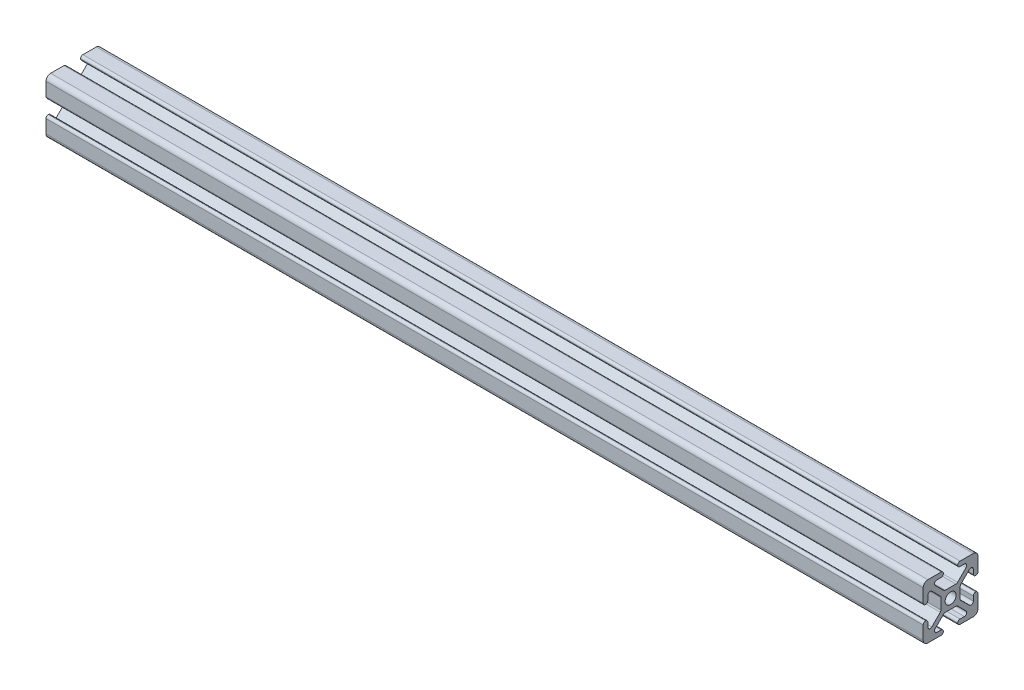
SolidWorks part; units mm, degrees
ref_plane "Front Plane" through (0, 0, 0) normal (1, 0, 0) x (0, 1, 0)
ref_plane "Top Plane" through (0, 0, 0) normal (0, 0, 1) x (0, 1, 0)
ref_plane "Right Plane" through (0, 0, 0) normal (0, 1, 0) x (-1, 0, 0)
sketch "Sketch1" plane through (0, 0, 0) normal (1, 0, 0) x (0, 1, 0)
  line L0 (0, 0) -> (0, 12.5) construction
  line L1 (-12.5, -12.5) -> (12.5, -12.5)
  line L2 (-12.5, -12.5) -> (-12.5, 12.5)
  line L3 (-12.5, 12.5) -> (12.5, 12.5)
  line L4 (12.5, -12.5) -> (12.5, 12.5)
  line L5 (-12.5, -12.5) -> (12.5, 12.5) construction
  line L6 (-12.5, 12.5) -> (12.5, -12.5) construction
  line L7 (-3.25, 12.5) -> (-3.25, 10.37)
  line L8 (-3.25, 10.37) -> (-8.8639, 10.37)
  line L9 (-8.8639, 10.37) -> (-2.8739, 4.38)
  line L10 (-2.8739, 4.38) -> (2.8739, 4.38)
  line L11 (8.8639, 10.37) -> (2.8739, 4.38)
  line L12 (3.25, 10.37) -> (8.8639, 10.37)
  line L13 (3.25, 12.5) -> (3.25, 10.37)
  line L14 (12.5, -3.25) -> (10.37, -3.25)
  line L15 (10.37, -3.25) -> (10.37, -8.8639)
  line L16 (10.37, -8.8639) -> (4.38, -2.8739)
  line L17 (4.38, 2.8739) -> (4.38, -2.8739)
  line L18 (10.37, 8.8639) -> (4.38, 2.8739)
  line L19 (10.37, 3.25) -> (10.37, 8.8639)
  line L20 (12.5, 3.25) -> (10.37, 3.25)
  line L21 (-3.25, -12.5) -> (-3.25, -10.37)
  line L22 (-3.25, -10.37) -> (-8.8639, -10.37)
  line L23 (-8.8639, -10.37) -> (-2.8739, -4.38)
  line L24 (2.8739, -4.38) -> (-2.8739, -4.38)
  line L25 (8.8639, -10.37) -> (2.8739, -4.38)
  line L26 (3.25, -10.37) -> (8.8639, -10.37)
  line L27 (3.25, -12.5) -> (3.25, -10.37)
  line L28 (-12.5, 3.25) -> (-10.37, 3.25)
  line L29 (-10.37, 3.25) -> (-10.37, 8.8639)
  line L30 (-10.37, 8.8639) -> (-4.38, 2.8739)
  line L31 (-4.38, -2.8739) -> (-4.38, 2.8739)
  line L32 (-10.37, -8.8639) -> (-4.38, -2.8739)
  line L33 (-10.37, -3.25) -> (-10.37, -8.8639)
  line L34 (-12.5, -3.25) -> (-10.37, -3.25)
  circle A0 centre (0, 0) radius 2.5
  point P0 (0, 0)
  point P15 (0, 4.38)
  dimension "D3" = 5
  dimension "D1" = 25
  dimension "D2" = 25
  dimension "D4" = 2.13
  dimension "D5" = 2.13
  dimension "D6" = 6.5
  dimension "D7" = 4.38
  dimension "D8" = 4
extrude "Boss-Extrude1" add sketch "Sketch1" along normal blind 400 contours L34 L2 L1 L21 L22 L23 L24 L25 L26 L27 L4 L14 L15 L16 L17 L18 L19 L20 L3 L13 L12 L11 L10 L9 L8 L7 L28 L29 L30 L31 L32 L33 A0 region at (0, -12.1464, -7.875)
fillet "Fillet1" radius 1.065 32 edges at (200, -10.37, -8.8639) (200, 2.8739, -4.38) (200, -2.8739, -4.38) (200, -4.38, 2.8739) (200, -4.38, -2.8739) (200, -2.8739, 4.38) (200, 2.8739, 4.38) (200, 4.38, 2.8739) (200, 4.38, -2.8739) (200, -8.8639, -10.37) (200, 8.8639, -10.37) (200, 10.37, -8.8639) (200, -10.37, 8.8639) (200, -8.8639, 10.37) (200, 10.37, 8.8639) (200, 8.8639, 10.37) (200, 12.5, 3.25) (200, -3.25, -12.5) (200, -10.37, 3.25) (200, 10.37, 3.25) (200, -10.37, -3.25) (200, -12.5, -3.25) (200, -12.5, 3.25) (200, 3.25, -10.37) (200, -3.25, -10.37) (200, 3.25, -12.5) (200, 10.37, -3.25) (200, 12.5, -3.25) (200, 3.25, 12.5) (200, 3.25, 10.37) (200, -3.25, 10.37) (200, -3.25, 12.5)
fillet "Fillet2" radius 2.13 4 edges at (200, 12.5, -12.5) (200, -12.5, -12.5) (200, 12.5, 12.5) (200, -12.5, 12.5)
sketch "Sketch2" plane through (400, 0, 0) normal (1, 0, 0) x (0, 1, 0)
  line L0 (10.37, -12.5) -> (4.315, -12.5)
  line L1 (10.37, -12.5) -> (4.315, -12.5)
  line L2 (4.315, -10.37) -> (6.2927, -10.37)
  line L3 (4.315, -10.37) -> (6.2927, -10.37)
  line L4 (7.0458, -8.5519) -> (3.1858, -4.6919)
  line L5 (7.0458, -8.5519) -> (3.1858, -4.6919)
  line L6 (2.4327, -4.38) -> (-2.4327, -4.38)
  line L7 (2.4327, -4.38) -> (-2.4327, -4.38)
  line L8 (-3.1858, -4.6919) -> (-7.0458, -8.5519)
  line L9 (-3.1858, -4.6919) -> (-7.0458, -8.5519)
  line L10 (-6.2927, -10.37) -> (-4.315, -10.37)
  line L11 (-6.2927, -10.37) -> (-4.315, -10.37)
  line L12 (-4.315, -12.5) -> (-10.37, -12.5)
  line L13 (-4.315, -12.5) -> (-10.37, -12.5)
  line L14 (-12.5, -10.37) -> (-12.5, -4.315)
  line L15 (-12.5, -10.37) -> (-12.5, -4.315)
  line L16 (-10.37, -4.315) -> (-10.37, -6.2927)
  line L17 (-10.37, -4.315) -> (-10.37, -6.2927)
  line L18 (-8.5519, -7.0458) -> (-4.6919, -3.1858)
  line L19 (-8.5519, -7.0458) -> (-4.6919, -3.1858)
  line L20 (-4.38, -2.4327) -> (-4.38, 2.4327)
  line L21 (-4.38, -2.4327) -> (-4.38, 2.4327)
  line L22 (-4.6919, 3.1858) -> (-8.5519, 7.0458)
  line L23 (-4.6919, 3.1858) -> (-8.5519, 7.0458)
  line L24 (-10.37, 6.2927) -> (-10.37, 4.315)
  line L25 (-10.37, 6.2927) -> (-10.37, 4.315)
  line L26 (-12.5, 4.315) -> (-12.5, 10.37)
  line L27 (-12.5, 4.315) -> (-12.5, 10.37)
  line L28 (-10.37, 12.5) -> (-4.315, 12.5)
  line L29 (-10.37, 12.5) -> (-4.315, 12.5)
  line L30 (-4.315, 10.37) -> (-6.2927, 10.37)
  line L31 (-4.315, 10.37) -> (-6.2927, 10.37)
  line L32 (-7.0458, 8.5519) -> (-3.1858, 4.6919)
  line L33 (-7.0458, 8.5519) -> (-3.1858, 4.6919)
  line L34 (-2.4327, 4.38) -> (2.4327, 4.38)
  line L35 (-2.4327, 4.38) -> (2.4327, 4.38)
  line L36 (3.1858, 4.6919) -> (7.0458, 8.5519)
  line L37 (3.1858, 4.6919) -> (7.0458, 8.5519)
  line L38 (6.2927, 10.37) -> (4.315, 10.37)
  line L39 (6.2927, 10.37) -> (4.315, 10.37)
  line L40 (4.315, 12.5) -> (10.37, 12.5)
  line L41 (4.315, 12.5) -> (10.37, 12.5)
  line L42 (12.5, 10.37) -> (12.5, 4.315)
  line L43 (12.5, 10.37) -> (12.5, 4.315)
  line L44 (10.37, 4.315) -> (10.37, 6.2927)
  line L45 (10.37, 4.315) -> (10.37, 6.2927)
  line L46 (8.5519, 7.0458) -> (4.6919, 3.1858)
  line L47 (8.5519, 7.0458) -> (4.6919, 3.1858)
  line L48 (4.38, 2.4327) -> (4.38, -2.4327)
  line L49 (4.38, 2.4327) -> (4.38, -2.4327)
  line L50 (4.6919, -3.1858) -> (8.5519, -7.0458)
  line L51 (4.6919, -3.1858) -> (8.5519, -7.0458)
  line L52 (10.37, -6.2927) -> (10.37, -4.315)
  line L53 (10.37, -6.2927) -> (10.37, -4.315)
  line L54 (12.5, -4.315) -> (12.5, -10.37)
  line L55 (12.5, -4.315) -> (12.5, -10.37)
  arc A0 (10.37, -12.5) -> (12.5, -10.37) centre (10.37, -10.37) ccw
  circle A1 centre (0, 0) radius 2.5
  circle A2 centre (0, 0) radius 2.5
  arc A3 (10.37, -12.5) -> (12.5, -10.37) centre (10.37, -10.37) ccw
  arc A4 (3.25, -11.435) -> (4.315, -12.5) centre (4.315, -11.435) ccw
  arc A5 (3.25, -11.435) -> (4.315, -12.5) centre (4.315, -11.435) ccw
  arc A6 (4.315, -10.37) -> (3.25, -11.435) centre (4.315, -11.435) ccw
  arc A7 (4.315, -10.37) -> (3.25, -11.435) centre (4.315, -11.435) ccw
  arc A8 (6.2927, -10.37) -> (7.0458, -8.5519) centre (6.2927, -9.305) ccw
  arc A9 (6.2927, -10.37) -> (7.0458, -8.5519) centre (6.2927, -9.305) ccw
  arc A10 (3.1858, -4.6919) -> (2.4327, -4.38) centre (2.4327, -5.445) ccw
  arc A11 (3.1858, -4.6919) -> (2.4327, -4.38) centre (2.4327, -5.445) ccw
  arc A12 (-2.4327, -4.38) -> (-3.1858, -4.6919) centre (-2.4327, -5.445) ccw
  arc A13 (-2.4327, -4.38) -> (-3.1858, -4.6919) centre (-2.4327, -5.445) ccw
  arc A14 (-7.0458, -8.5519) -> (-6.2927, -10.37) centre (-6.2927, -9.305) ccw
  arc A15 (-7.0458, -8.5519) -> (-6.2927, -10.37) centre (-6.2927, -9.305) ccw
  arc A16 (-3.25, -11.435) -> (-4.315, -10.37) centre (-4.315, -11.435) ccw
  arc A17 (-3.25, -11.435) -> (-4.315, -10.37) centre (-4.315, -11.435) ccw
  arc A18 (-4.315, -12.5) -> (-3.25, -11.435) centre (-4.315, -11.435) ccw
  arc A19 (-4.315, -12.5) -> (-3.25, -11.435) centre (-4.315, -11.435) ccw
  arc A20 (-12.5, -10.37) -> (-10.37, -12.5) centre (-10.37, -10.37) ccw
  arc A21 (-12.5, -10.37) -> (-10.37, -12.5) centre (-10.37, -10.37) ccw
  arc A22 (-11.435, -3.25) -> (-12.5, -4.315) centre (-11.435, -4.315) ccw
  arc A23 (-11.435, -3.25) -> (-12.5, -4.315) centre (-11.435, -4.315) ccw
  arc A24 (-10.37, -4.315) -> (-11.435, -3.25) centre (-11.435, -4.315) ccw
  arc A25 (-10.37, -4.315) -> (-11.435, -3.25) centre (-11.435, -4.315) ccw
  arc A26 (-10.37, -6.2927) -> (-8.5519, -7.0458) centre (-9.305, -6.2927) ccw
  arc A27 (-10.37, -6.2927) -> (-8.5519, -7.0458) centre (-9.305, -6.2927) ccw
  arc A28 (-4.6919, -3.1858) -> (-4.38, -2.4327) centre (-5.445, -2.4327) ccw
  arc A29 (-4.6919, -3.1858) -> (-4.38, -2.4327) centre (-5.445, -2.4327) ccw
  arc A30 (-4.38, 2.4327) -> (-4.6919, 3.1858) centre (-5.445, 2.4327) ccw
  arc A31 (-4.38, 2.4327) -> (-4.6919, 3.1858) centre (-5.445, 2.4327) ccw
  arc A32 (-8.5519, 7.0458) -> (-10.37, 6.2927) centre (-9.305, 6.2927) ccw
  arc A33 (-8.5519, 7.0458) -> (-10.37, 6.2927) centre (-9.305, 6.2927) ccw
  arc A34 (-11.435, 3.25) -> (-10.37, 4.315) centre (-11.435, 4.315) ccw
  arc A35 (-11.435, 3.25) -> (-10.37, 4.315) centre (-11.435, 4.315) ccw
  arc A36 (-12.5, 4.315) -> (-11.435, 3.25) centre (-11.435, 4.315) ccw
  arc A37 (-12.5, 4.315) -> (-11.435, 3.25) centre (-11.435, 4.315) ccw
  arc A38 (-10.37, 12.5) -> (-12.5, 10.37) centre (-10.37, 10.37) ccw
  arc A39 (-10.37, 12.5) -> (-12.5, 10.37) centre (-10.37, 10.37) ccw
  arc A40 (-3.25, 11.435) -> (-4.315, 12.5) centre (-4.315, 11.435) ccw
  arc A41 (-3.25, 11.435) -> (-4.315, 12.5) centre (-4.315, 11.435) ccw
  arc A42 (-4.315, 10.37) -> (-3.25, 11.435) centre (-4.315, 11.435) ccw
  arc A43 (-4.315, 10.37) -> (-3.25, 11.435) centre (-4.315, 11.435) ccw
  arc A44 (-6.2927, 10.37) -> (-7.0458, 8.5519) centre (-6.2927, 9.305) ccw
  arc A45 (-6.2927, 10.37) -> (-7.0458, 8.5519) centre (-6.2927, 9.305) ccw
  arc A46 (-3.1858, 4.6919) -> (-2.4327, 4.38) centre (-2.4327, 5.445) ccw
  arc A47 (-3.1858, 4.6919) -> (-2.4327, 4.38) centre (-2.4327, 5.445) ccw
  arc A48 (2.4327, 4.38) -> (3.1858, 4.6919) centre (2.4327, 5.445) ccw
  arc A49 (2.4327, 4.38) -> (3.1858, 4.6919) centre (2.4327, 5.445) ccw
  arc A50 (7.0458, 8.5519) -> (6.2927, 10.37) centre (6.2927, 9.305) ccw
  arc A51 (7.0458, 8.5519) -> (6.2927, 10.37) centre (6.2927, 9.305) ccw
  arc A52 (3.25, 11.435) -> (4.315, 10.37) centre (4.315, 11.435) ccw
  arc A53 (3.25, 11.435) -> (4.315, 10.37) centre (4.315, 11.435) ccw
  arc A54 (4.315, 12.5) -> (3.25, 11.435) centre (4.315, 11.435) ccw
  arc A55 (4.315, 12.5) -> (3.25, 11.435) centre (4.315, 11.435) ccw
  arc A56 (12.5, 10.37) -> (10.37, 12.5) centre (10.37, 10.37) ccw
  arc A57 (12.5, 10.37) -> (10.37, 12.5) centre (10.37, 10.37) ccw
  arc A58 (11.435, 3.25) -> (12.5, 4.315) centre (11.435, 4.315) ccw
  arc A59 (11.435, 3.25) -> (12.5, 4.315) centre (11.435, 4.315) ccw
  arc A60 (10.37, 4.315) -> (11.435, 3.25) centre (11.435, 4.315) ccw
  arc A61 (10.37, 4.315) -> (11.435, 3.25) centre (11.435, 4.315) ccw
  arc A62 (10.37, 6.2927) -> (8.5519, 7.0458) centre (9.305, 6.2927) ccw
  arc A63 (10.37, 6.2927) -> (8.5519, 7.0458) centre (9.305, 6.2927) ccw
  arc A64 (4.6919, 3.1858) -> (4.38, 2.4327) centre (5.445, 2.4327) ccw
  arc A65 (4.6919, 3.1858) -> (4.38, 2.4327) centre (5.445, 2.4327) ccw
  arc A66 (4.38, -2.4327) -> (4.6919, -3.1858) centre (5.445, -2.4327) ccw
  arc A67 (4.38, -2.4327) -> (4.6919, -3.1858) centre (5.445, -2.4327) ccw
  arc A68 (8.5519, -7.0458) -> (10.37, -6.2927) centre (9.305, -6.2927) ccw
  arc A69 (8.5519, -7.0458) -> (10.37, -6.2927) centre (9.305, -6.2927) ccw
  arc A70 (11.435, -3.25) -> (10.37, -4.315) centre (11.435, -4.315) ccw
  arc A71 (11.435, -3.25) -> (10.37, -4.315) centre (11.435, -4.315) ccw
  arc A72 (12.5, -4.315) -> (11.435, -3.25) centre (11.435, -4.315) ccw
  arc A73 (12.5, -4.315) -> (11.435, -3.25) centre (11.435, -4.315) ccw
  dimension "D1" = 0
